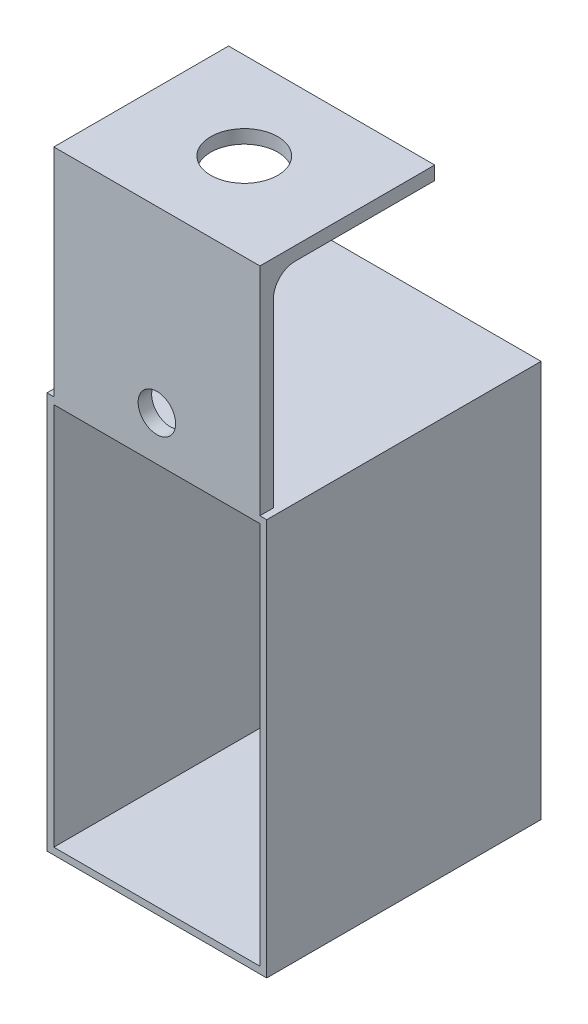
SolidWorks part; units mm, degrees
ref_plane "Front Plane" through (0, 0, 0) normal (0, 0, 1) x (1, 0, 0)
ref_plane "Top Plane" through (0, 0, 0) normal (0, 1, 0) x (1, 0, 0)
ref_plane "Right Plane" through (0, 0, 0) normal (1, 0, 0) x (0, 0, -1)
sketch "Sketch1" plane through (0, 0, 0) normal (0, 0, 1) x (1, 0, 0)
  line L1 (12.9, -23.3) -> (-12.9, -23.3)
  line L2 (12.9, -23.3) -> (12.9, 23.3)
  line L3 (12.9, 23.3) -> (-12.9, 23.3)
  line L4 (-12.9, -23.3) -> (-12.9, 23.3)
  line L5 (12.9, -23.3) -> (-12.9, 23.3) construction
  line L6 (12.9, 23.3) -> (-12.9, -23.3) construction
  point P0 (0, 0)
  dimension "D1" = 25.8
  dimension "D2" = 46.6
extrude "Boss-Extrude1" add sketch "Sketch1" along normal blind 32.2
shell "Shell1" thickness 0.8 removed face at (0, 0, 32.2)
sketch "Sketch2" plane through (0, 0, 32.2) normal (0, 0, 1) x (1, 0, 0)
  line L0 (12.9, 23.3) -> (-12.9, 23.3) construction
  line L1 (-12.1, 23.3) -> (12.1, 23.3)
  line L2 (-12.1, 23.3) -> (-12.1, 48.7)
  line L3 (-12.1, 48.7) -> (12.1, 48.7)
  line L4 (12.1, 23.3) -> (12.1, 48.7)
  line L5 (-12.1, 22.5) -> (-12.1, -22.5) construction
  line L6 (12.1, -22.5) -> (12.1, 22.5) construction
  dimension "D2" = 25.4
extrude "Boss-Extrude2" add sketch "Sketch2" against normal blind 1.5875
sketch "Sketch3" plane through (0, 0, 30.6125) normal (0, 0, -1) x (-1, 0, 0)
  line L0 (-12.9, 23.3) -> (12.9, 23.3) construction
  line L1 (-12.1, 23.3) -> (-12.1, 48.7) construction
  circle A0 centre (0, 27.7) radius 2.2
  dimension "D1" = 4.4
  dimension "D2" = 4.4
  dimension "D3" = 12.1
extrude "Cut-Extrude1" cut sketch "Sketch3" against normal through all contours A0
sketch "Sketch5" plane through (0, 48.7, 0) normal (0, 1, 0) x (1, 0, 0)
  line L0 (12.1, -30.6125) -> (12.1, -32.2) construction
  line L1 (-12.1, -30.6125) -> (12.1, -30.6125)
  line L2 (-12.1, -30.6125) -> (-12.1, -11.6782)
  line L3 (-12.1, -11.6782) -> (12.1, -11.6782)
  line L4 (12.1, -30.6125) -> (12.1, -11.6782)
  dimension "D1" = 18.9343
extrude "Boss-Extrude3" add sketch "Sketch5" against normal blind 1.5875
sketch "Sketch7" plane through (0, 48.7, 0) normal (0, 1, 0) x (1, 0, 0)
  line L0 (0, -11.6782) -> (0, -32.2) construction
  line L1 (12.1, -11.6782) -> (-12.1, -11.6782) construction
  line L2 (12.1, -32.2) -> (-12.1, -32.2) construction
  line L3 (-12.1, -21.9391) -> (12.1, -21.9391) construction
  line L4 (-12.1, -11.6782) -> (-12.1, -32.2) construction
  line L5 (12.1, -11.6782) -> (12.1, -32.2) construction
  circle A0 centre (0, -21.9391) radius 3.937
  dimension "D1" = 7.874
extrude "Cut-Extrude2" cut sketch "Sketch7" against normal up to surface (25.4 mm away) contours A0 up to face at (0, 23.3, 23.7531)
fillet "Fillet1" radius 2.54 1 edges at (0, 47.1125, 30.6125) type face fillet first side face at (0, 47.1125, 18.0021) second side face at (0, 35.2063, 30.6125)
